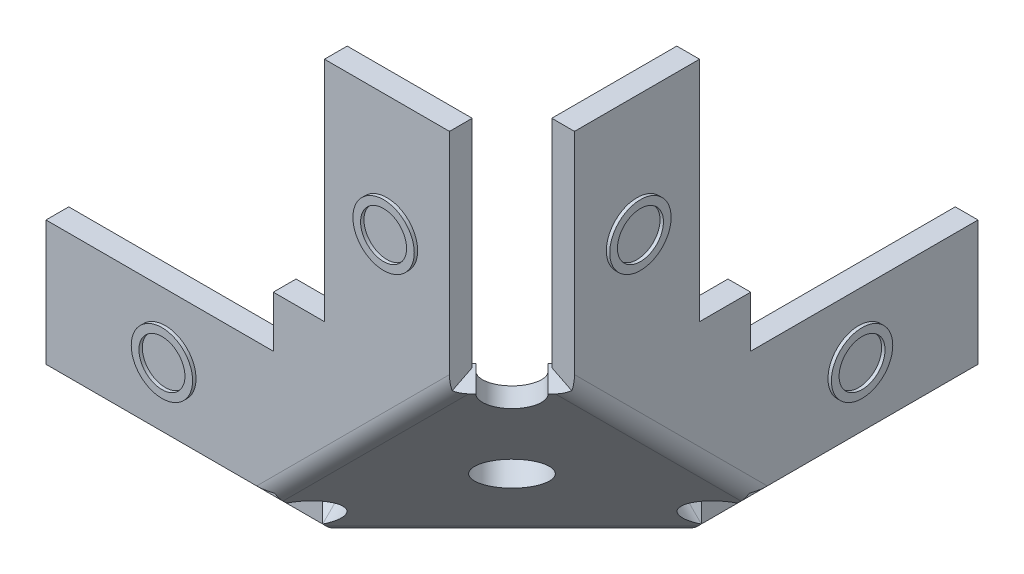
SolidWorks part; units mm, degrees
note: '?' marks a value the reader was unsure of.
ref_plane "Front Plane" through (0, 0, 0) normal (0, 0, 1) x (1, 0, 0)
ref_plane "Top Plane" through (0, 0, 0) normal (0, 1, 0) x (1, 0, 0)
ref_plane "Right Plane" through (0, 0, 0) normal (1, 0, 0) x (0, 0, -1)
sketch "Sketch1" plane through (0, 0, 0) normal (0, 0, 1) x (1, 0, 0)
  line L0 (0, 0) -> (-35, 0) construction
  line L1 (-5, 5) -> (-35, 5) construction
  line L2 (-5, 5) -> (-5, -5) construction
  line L3 (-5, -5) -> (-35, -5) construction
  line L4 (-35, 5) -> (-35, -5) construction
  line L5 (-5, 35) -> (5, 35) construction
  line L6 (-5, 35) -> (-5, 5) construction
  line L7 (-5, 5) -> (5, 5) construction
  line L8 (5, 35) -> (5, 5) construction
  line L9 (0, 0) -> (0, 35) construction
  line L10 (-5, 2.75) -> (-5, 5)
  line L11 (-15, 2.75) -> (-5, 2.75)
  line L12 (-15, 2.75) -> (-15, -2.75)
  line L13 (-15, -2.75) -> (-5, -2.75)
  line L15 (-2.75, 15) -> (2.75, 15)
  line L16 (-2.75, 15) -> (-2.75, 5)
  line L18 (2.75, 15) -> (2.75, 5)
  line L19 (-5, 5) -> (-2.75, 5)
  line L20 (2.75, 5) -> (-5, -2.75)
  circle A0 centre (0, 9.75) radius 1.35 construction
  circle A1 centre (-9.75, 0) radius 1.35 construction
  point P19 (0, 15)
  point P20 (-15, 0)
  dimension "D7" = 2.7
  dimension "D1" = 10
  dimension "D2" = 30
  dimension "D3" = 5.5
  dimension "D4" = 10
  dimension "D5" = 5.25
  dimension "D6" = 5.25
extrude "Boss-Extrude1" add sketch "Sketch1" along normal mid plane 1
ref_axis "Axis1" through (-5, -5, 0) along (-1, 0, 0)?
ref_axis "Axis2" through (5, 35, 0) along (0, -1, 0)?
sketch "Sketch6" plane through (0, -0.5, 0) normal (0, 0, -1) x (-1, 0, 0)
  circle A3 centre (0, 10.25) radius 1.1
  circle A4 centre (0, 10.25) radius 1.1
  circle A5 centre (9.75, 0.5) radius 1.1
  circle A6 centre (9.75, 0.5) radius 1.1
  dimension "D1" = 0.25
  dimension "D2" = 0.25
extrude "Boss-Extrude3" add sketch "Sketch6" along normal mid plane 3 draft 10
chamfer "Chamfer1" distance 0.2 angle 45 4 edges at (-10.5855, 0, -1.5) (-0.8355, 9.75, -1.5) (-0.8355, 9.75, 1.5) (-10.5855, 0, 1.5)
pattern_circular "CirPattern2" count 2 every 270 about axis through (0, -5, 0) along (1, 0, 0) of bodies 110 101
pattern_circular "CirPattern3" count 2 every 90 about axis through (5, 0, 0) along (0, 1, 0) of bodies 110 101
sketch "Sketch9" plane through (0, -5.5, 0) normal (0, -1, 0) x (1, 0, 0)
  line L9 (-5, -10) -> (-2.75, -10)
  line L10 (-2.75, -10) -> (-2.75, -20)
  line L11 (-2.75, -20) -> (2.75, -20)
  line L12 (2.75, -20) -> (2.75, -10)
  line L13 (2.75, -10) -> (-5, -2.25)
  line L14 (-5, -2.25) -> (-15, -2.25)
  line L15 (-15, -2.25) -> (-15, -7.75)
  line L16 (-15, -7.75) -> (-5, -7.75)
  line L17 (-5, -7.75) -> (-5, -10)
  line L18 (-5, -10) -> (-2.75, -10)
  line L19 (-2.75, -10) -> (-2.75, -20)
  line L20 (-2.75, -20) -> (2.75, -20)
  line L21 (2.75, -20) -> (2.75, -10)
  line L22 (2.75, -10) -> (-5, -2.25)
  line L23 (-5, -2.25) -> (-15, -2.25)
  line L24 (-15, -2.25) -> (-15, -7.75)
  line L25 (-15, -7.75) -> (-5, -7.75)
  line L26 (-5, -7.75) -> (-5, -10)
  dimension "D1" = 0
extrude "Cut-Extrude8" cut sketch "Sketch9" along normal through all
sketch "Sketch10" plane through (0, 0, 0.5) normal (0, 0, 1) x (1, 0, 0)
  line L9 (-2.75, 5) -> (-5, 5)
  line L10 (-5, 5) -> (-5, 2.75)
  line L11 (-5, 2.75) -> (-15, 2.75)
  line L12 (-15, 2.75) -> (-15, -2.75)
  line L13 (-15, -2.75) -> (-5, -2.75)
  line L14 (-5, -2.75) -> (2.75, 5)
  line L15 (2.75, 5) -> (2.75, 15)
  line L16 (2.75, 15) -> (-2.75, 15)
  line L17 (-2.75, 15) -> (-2.75, 5)
  line L18 (-2.75, 5) -> (-5, 5)
  line L19 (-5, 5) -> (-5, 2.75)
  line L20 (-5, 2.75) -> (-15, 2.75)
  line L21 (-15, 2.75) -> (-15, -2.75)
  line L22 (-15, -2.75) -> (-5, -2.75)
  line L23 (-5, -2.75) -> (2.75, 5)
  line L24 (2.75, 5) -> (2.75, 15)
  line L25 (2.75, 15) -> (-2.75, 15)
  line L26 (-2.75, 15) -> (-2.75, 5)
  dimension "D1" = 0
extrude "Cut-Extrude10" cut sketch "Sketch10" along normal through all
sketch "Sketch11" plane through (5.5, 0, 0) normal (1, 0, 0) x (0, 0, -1)
  line L9 (10, 5) -> (7.75, 5)
  line L10 (7.75, 5) -> (7.75, 15)
  line L11 (7.75, 15) -> (2.25, 15)
  line L12 (2.25, 15) -> (2.25, 5)
  line L13 (2.25, 5) -> (10, -2.75)
  line L14 (10, -2.75) -> (20, -2.75)
  line L15 (20, -2.75) -> (20, 2.75)
  line L16 (20, 2.75) -> (10, 2.75)
  line L17 (10, 2.75) -> (10, 5)
  line L18 (10, 5) -> (7.75, 5)
  line L19 (7.75, 5) -> (7.75, 15)
  line L20 (7.75, 15) -> (2.25, 15)
  line L21 (2.25, 15) -> (2.25, 5)
  line L22 (2.25, 5) -> (10, -2.75)
  line L23 (10, -2.75) -> (20, -2.75)
  line L24 (20, -2.75) -> (20, 2.75)
  line L25 (20, 2.75) -> (10, 2.75)
  line L26 (10, 2.75) -> (10, 5)
  dimension "D1" = 0
extrude "Cut-Extrude11" cut sketch "Sketch11" along normal through all
sketch "Sketch8" plane through (0, 0, 0.5) normal (0, 0, 1) x (1, 0, 0)
  circle A0 centre (-9.75, 0) radius 1.35 construction
  circle A1 centre (0, 9.75) radius 1.35 construction
  circle A2 centre (-9.75, 0) radius 1.35
  circle A3 centre (0, 9.75) radius 1.35
  circle A4 centre (-9.75, 0) radius 1.0118 construction
  circle A5 centre (0, 9.75) radius 1.0118 construction
  circle A6 centre (-9.75, 0) radius 1.0118
  circle A7 centre (0, 9.75) radius 1.0118
extrude "Boss-Extrude4" add sketch "Sketch8" along normal blind 0.15
sketch "Sketch12" plane through (0, -5.5, 0) normal (0, -1, 0) x (1, 0, 0)
  circle A0 centre (-9.75, -5) radius 1.0118 construction
  circle A1 centre (0, -14.75) radius 1.0118 construction
  circle A2 centre (-9.75, -5) radius 1.0118
  circle A3 centre (0, -14.75) radius 1.0118
  circle A4 centre (-9.75, -5) radius 1.35
  circle A5 centre (0, -14.75) radius 1.35
  dimension "D1" = 2.7
extrude "Boss-Extrude5" add sketch "Sketch12" along normal blind 0.15
sketch "Sketch13" plane through (5.5, 0, 0) normal (1, 0, 0) x (0, 0, -1)
  circle A0 centre (5, 9.75) radius 1.0118 construction
  circle A1 centre (14.75, 0) radius 1.0118 construction
  circle A2 centre (5, 9.75) radius 1.0118
  circle A3 centre (14.75, 0) radius 1.0118
  circle A4 centre (14.75, 0) radius 1.35
  circle A5 centre (5, 9.75) radius 1.35
  dimension "D1" = 2.7
extrude "Boss-Extrude6" add sketch "Sketch13" along normal blind 0.15
ref_plane "Plane1" through (-0.5833, 0.5833, -0.5833) normal (-0.5774, 0.5774, -0.5774) x (0.8165, 0.4082, -0.4082)
sketch "Sketch2" plane through (-0.5833, 0.5833, -0.5833) normal (-0.5774, 0.5774, -0.5774) x (0.8165, 0.4082, -0.4082)
  line L0 (7.4505, 9.0156) -> (7.4505, -1.9445) construction
  line L1 (-5.4093, 5.4801) -> (4.0825, 10.9602) construction
  line L2 (-5.4093, 1.591) -> (4.0825, -3.8891) construction
  line L3 (7.4505, 9.0156) -> (7.4505, -1.9445)
  line L4 (-5.4093, 5.4801) -> (4.0825, 10.9602)
  line L5 (-5.4093, 1.591) -> (4.0825, -3.8891)
  line L6 (4.0825, 10.9602) -> (7.4505, 9.0156)
  line L7 (4.0825, -3.8891) -> (7.4505, -1.9445)
  line L8 (-5.4093, 1.591) -> (-5.4093, 5.4801)
  line L9 (-5.4093, 3.5355) -> (2.0412, 3.5355) construction
  line L10 (5.7665, 9.9879) -> (2.0412, 3.5355) construction
  line L11 (5.7665, -2.9168) -> (2.0412, 3.5355) construction
  circle A0 centre (2.0412, 3.5355) radius 1.35
  dimension "D1" = 2.7
extrude "Boss-Extrude2" add sketch "Sketch2" along normal blind 1
fillet "Fillet1" radius 1 3 edges at (5.5, 1.125, -6.125) (-1.125, -5.5, -6.125) (-1.125, 1.125, 0.5)
ref_plane "Plane2" through (4.125, -4.125, 0) normal (-0.7071, 0.7071, 0) x (0.7071, 0.7071, 0)
sketch "Sketch3" plane through (4.125, -4.125, 0) normal (-0.7071, 0.7071, 0) x (0.7071, 0.7071, 0)
  line L0 (1.3468, 10) -> (-1.3468, 10) construction
  line L1 (1.125, 10) -> (1.125, 11.125)
  line L2 (1.125, 11.125) -> (-1.125, 11.125)
  line L3 (-1.125, 11.125) -> (-1.125, 10)
  arc A0 (-1.125, 10) -> (1.125, 10) centre (0, 10) ccw
  dimension "D1" = 2.25
extrude "Cut-Extrude2" cut sketch "Sketch3" along normal through all
ref_plane "Plane3" through (1.625, 0, 1.625) normal (-0.7071, 0, -0.7071) x (-0.7071, 0, 0.7071)
sketch "Sketch4" plane through (1.625, 0, 1.625) normal (-0.7071, 0, -0.7071) x (-0.7071, 0, 0.7071)
  line L0 (-2.1887, 5) -> (-4.8824, 5) construction
  line L1 (-2.4105, 5) -> (-2.4105, 6.125)
  line L2 (-2.4105, 6.125) -> (-4.6605, 6.125)
  line L3 (-4.6605, 6.125) -> (-4.6605, 5)
  arc A0 (-4.6605, 5) -> (-2.4105, 5) centre (-3.5355, 5) ccw
  dimension "D1" = 1.125
extrude "Cut-Extrude4" cut sketch "Sketch4" along normal through all
ref_plane "Plane4" through (0, -1.625, 1.625) normal (0, 0.7071, -0.7071) x (-1, 0, 0)
sketch "Sketch5" plane through (0, -1.625, 1.625) normal (0, 0.7071, -0.7071) x (-1, 0, 0)
  line L0 (5, -4.8824) -> (5, -2.1887) construction
  line L1 (5, -4.6605) -> (6.125, -4.6605)
  line L2 (6.125, -4.6605) -> (6.125, -2.4105)
  line L3 (5, -2.4105) -> (6.125, -2.4105)
  arc A0 (5, -2.4105) -> (5, -4.6605) centre (5, -3.5355) ccw
  dimension "D1" = 2.25
extrude "Cut-Extrude6" cut sketch "Sketch5" along normal blind 4
equation "\"D6@Sketch1\"=\"D5@Sketch1\""
